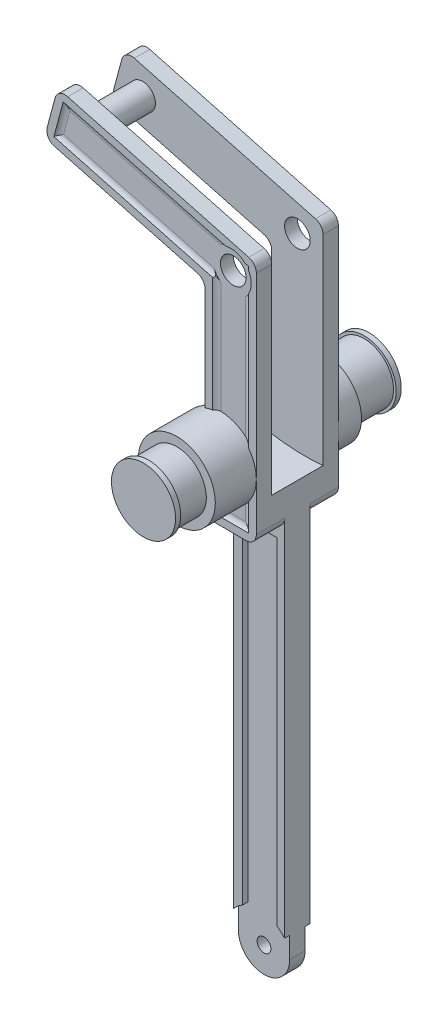
SolidWorks part; units mm, degrees
note: The reader was unsure of these and kept them because the rebuilt part matched: shared geometry of "Schizzo1<5>".
ref_plane "Piano frontale" through (0, 0, 0) normal (0, 0, 1) x (1, 0, 0)
ref_plane "Piano superiore" through (0, 0, 0) normal (0, 1, 0) x (1, 0, 0)
ref_plane "Piano destro" through (0, 0, 0) normal (1, 0, 0) x (0, 0, -1)
sketch "Schizzo1" plane through (0, 0, 0) normal (0, 0, 1) x (1, 0, 0)
  line L0 (0, -1.5347) -> (0, -38)
  line L9 (2, -40) -> (8, -40)
  line L10 (10, -38) -> (10, 6.1386)
  line L11 (8.5176, 8.0705) -> (-26.7741, 17.5268)
  line L12 (-29.2235, 16.1126) -> (-30.7765, 10.3171)
  line L13 (-29.3622, 7.8676) -> (-1.4824, 0.3972)
  line L14 (-19.0466, 15.4563) -> (-21.6348, 5.797) construction
  line L15 (-21.6348, 5.797) -> (-20.3407, 10.6267) construction
  line L16 (-20.3407, 10.6267) -> (-30, 13.2149) construction
  line L17 (-30, 13.2149) -> (-29.4183, 13.059) construction
  arc A0 (2, -40) -> (0, -38) centre (2, -38) cw
  arc A1 (8, -40) -> (10, -38) centre (8, -38) ccw
  arc A2 (0, -1.5347) -> (-1.4824, 0.3972) centre (-2, -1.5347) ccw
  arc A3 (10, 6.1386) -> (8.5176, 8.0705) centre (8, 6.1386) ccw
  arc A4 (-29.2235, 16.1126) -> (-26.7741, 17.5268) centre (-27.2917, 15.595) cw
  arc A5 (-29.3622, 7.8676) -> (-30.7765, 10.3171) centre (-28.8446, 9.7994) cw
  point P2 (-30, 13.2149)
  point P19 (0, 0)
  dimension "D6" = 2
  dimension "D1" = 40
  dimension "D2" = 40
  dimension "D3" = 10
  dimension "D4" = 10
  dimension "D5" = 10
  dimension "D7" = 105
extrude "Estrusione-Estrusione1" add sketch "Schizzo1" against normal blind 3 contours L11 A4 L12 A5 L13 A2 L0 A0 L9 A1 L10 A3
sketch "Schizzo4" plane through (0, 0, -3) normal (0, 0, -1) x (-1, 0, 0)
  line L0 (-8.5176, 8.0705) -> (26.7741, 17.5268) construction
  line L3 (29.2235, 16.1126) -> (30.7765, 10.3171) construction
  circle A0 centre (25.1704, 11.9208) radius 2.5
  dimension "D3" = 5
  dimension "D1" = 5
  dimension "D2" = 5
extrude "Estrusione-Estrusione4" add sketch "Schizzo4" along normal blind 5
sketch "Schizzo5" plane through (0, 0, -3) normal (0, 0, -1) x (-1, 0, 0)
  line L0 (-10, -32.8544) -> (-10, -38)
  line L1 (-10, -38) -> (-10, 6.1386) construction
  line L2 (0, -32.477) -> (0, -38)
  line L3 (0, -1.5347) -> (0, -38) construction
  line L4 (-2, -40) -> (-8, -40)
  arc A0 (-2, -40) -> (0, -38) centre (-2, -38) ccw
  arc A1 (-10, -32.8544) -> (0, -32.477) centre (-6.4967, 6.9919) ccw
  arc A2 (-8, -40) -> (-10, -38) centre (-8, -38) cw
  dimension "D1" = 40
extrude "Estrusione-Estrusione5" add sketch "Schizzo5" along normal blind 10
mirror "Specchia5" of "Estrusione-Estrusione4", "Estrusione-Estrusione5"
extrude "Estrusione-Estrusione6" add sketch "Schizzo1<5>" against normal blind 3 from surface at -13 starting at face at (-27.6704, 11.9208, -13)
sketch "Schizzo1<5>" plane through (0, 0, 0) normal (0, 0, 1) x (1, 0, 0) same geometry as "Schizzo1"
ref_plane "Piano2" through (0, 0, -8) normal (0, 0, -1) x (-1, 0, 0)
sketch "Schizzo8" plane through (0, 0, -8) normal (0, 0, -1) x (-1, 0, 0)
  line L0 (-8, -40) -> (-2, -40)
  line L5 (0, -38) -> (0, -108)
  line L6 (-10, -38) -> (-10, -108)
  line L7 (-10, -108) -> (0, -108)
  arc A0 (-2, -40) -> (0, -38) centre (-2, -38) ccw
  arc A1 (-10, -38) -> (-8, -40) centre (-8, -38) ccw
  dimension "D1" = 70
extrude "Estrusione-Estrusione7" add sketch "Schizzo8" along normal mid plane 5 contours L5 L7 L6 A1 L0 A0
sketch "Schizzo9" plane through (0, 0, -16) normal (0, 0, -1) x (-1, 0, 0)
  line L0 (-8.5, -38.5) -> (-8.5, 6.5223)
  line L1 (-8.5, 6.5223) -> (27.6452, 16.2074)
  line L2 (27.6452, 16.2074) -> (29.457, 9.4459)
  line L3 (29.457, 9.4459) -> (-1.5, 1.151)
  line L4 (-1.5, 1.151) -> (-1.5, -38.5)
  line L5 (-1.5, -38.5) -> (-8.5, -38.5)
  line L6 (-10, -38) -> (-10, 6.1386) construction
  line L7 (0, -1.5347) -> (0, -38) construction
  line L8 (-8.5176, 8.0705) -> (26.7741, 17.5268) construction
  line L10 (29.2235, 16.1126) -> (30.7765, 10.3171) construction
  line L11 (-8, -40) -> (-2, -40) construction
  line L12 (29.3622, 7.8676) -> (1.4824, 0.3972) construction
  dimension "D1" = 1.5
  dimension "D2" = 1.5
  dimension "D3" = 1.5
  dimension "D4" = 1.5
  dimension "D5" = 1.5
  dimension "D6" = 1.5
extrude "Taglio-Estrusione1" cut sketch "Schizzo9" against normal mid plane 1
sketch "Schizzo10" plane through (0, 0, 0) normal (0, 0, 1) x (1, 0, 0)
  line L1 (8.5, 6.5223) -> (-27.6452, 16.2074)
  line L2 (-27.6452, 16.2074) -> (-29.457, 9.4459)
  line L4 (8.5, -0.7247) -> (8.5, -38.5)
  line L5 (8.5, -38.5) -> (1.5, -38.5)
  line L6 (8.5, 6.5223) -> (8.5, -0.7247)
  line L7 (-29.457, 9.4459) -> (1.5, 1.151)
  line L8 (1.5, 1.151) -> (1.5, -38.5)
  line L9 (8.5176, 8.0705) -> (-26.7741, 17.5268) construction
  line L10 (-29.2235, 16.1126) -> (-30.7765, 10.3171) construction
  line L12 (0, -1.5347) -> (0, -38) construction
  line L13 (10, -38) -> (10, 6.1386) construction
  line L14 (2, -40) -> (8, -40) construction
  line L15 (-29.3622, 7.8676) -> (-1.4824, 0.3972) construction
  dimension "D1" = 1.5
  dimension "D2" = 1.5
  dimension "D3" = 1.5
  dimension "D4" = 1.5
  dimension "D5" = 1.5
  dimension "D6" = 1.5
extrude "Taglio-Estrusione2" cut sketch "Schizzo10" against normal mid plane 1
fillet "Raccordo1" radius 1.5 12 edges at (5, -38.5, -0.5) (8.5, -15.9889, -0.5) (1.5, -18.6745, -0.5) (-13.9785, 5.2984, -0.5) (-28.5511, 12.8266, -0.5) (-9.5726, 11.3648, -0.5) (1.5, -18.6745, -15.5) (5, -38.5, -15.5) (8.5, -15.9889, -15.5) (-9.5726, 11.3648, -15.5) (-28.5511, 12.8266, -15.5) (-13.9785, 5.2984, -15.5)
sketch "Schizzo13" plane through (0, 0, -0.5) normal (0, 0, 1) x (1, 0, 0)
  line L0 (0, -1.5347) -> (0, -38) construction
  line L1 (8.5176, 8.0705) -> (-26.7741, 17.5268) construction
  circle A0 centre (5, 3.8366) radius 2.5
  dimension "D3" = 5
  dimension "D1" = 5
  dimension "D2" = 5
extrude "Taglio-Estrusione5" cut sketch "Schizzo13" against normal mid plane 550
sketch "Schizzo14" plane through (0, -108, 0) normal (0, -1, 0) x (1, 0, 0)
  line L5 (0, -5.5) -> (10, -5.5)
  line L6 (0, -5.5) -> (0, -10.5)
  line L7 (0, -10.5) -> (10, -10.5)
  line L8 (10, -5.5) -> (10, -10.5)
extrude "Estrusione-Estrusione8" add sketch "Schizzo14" along normal blind 10
sketch "Schizzo16" plane through (0, 0, -5.5) normal (0, 0, 1) x (1, 0, 0)
  line L0 (10, -118) -> (0, -118) construction
  line L1 (10, -38) -> (10, -118) construction
  line L2 (0, -113) -> (-2.5239, -113)
  line L4 (-2.5239, -113) -> (-2.5239, -123.194)
  line L9 (-2.5239, -123.194) -> (14.5898, -123.194)
  line L10 (14.5898, -123.194) -> (14.5898, -113)
  line L11 (14.5898, -113) -> (10, -113)
  arc A1 (0, -113) -> (10, -113) centre (5, -113) ccw
  dimension "D3" = 10
  dimension "D1" = 5
  dimension "D2" = 5
extrude "Taglio-Estrusione6" cut sketch "Schizzo16" against normal blind 10
sketch "Schizzo17" plane through (0, 0, -5.5) normal (0, 0, 1) x (1, 0, 0)
  line L0 (0, -38) -> (0, -113) construction
  circle A0 centre (5, -113) radius 1.35
  arc A1 (0, -113) -> (10, -113) centre (5, -113) ccw construction
  point P7 (5, -118)
  dimension "D1" = 2.7
  dimension "D2" = 5
  dimension "D3" = 5
extrude "Taglio-Estrusione7" cut sketch "Schizzo17" against normal blind 10
sketch "Schizzo18" plane through (0, 0, -10.5) normal (0, 0, -1) x (-1, 0, 0)
  line L0 (-8.5, -42) -> (-1.5, -42)
  line L1 (-1.5, -42) -> (-1.5, -107.5543)
  line L2 (-8.5, -42) -> (-8.5, -107.5543)
  line L3 (-10, -38) -> (-10, -113) construction
  line L4 (0, -38) -> (0, -113) construction
  line L5 (-8, -40) -> (-2, -40) construction
  line L6 (-1.5, -107.5543) -> (-8.5, -107.5543) construction
  arc A1 (-8.5, -107.5543) -> (-1.5, -107.5543) centre (-5, -113) ccw
  dimension "D1" = 1.5
  dimension "D2" = 1.5
  dimension "D3" = 2
  dimension "D4" = 65.5543
extrude "Taglio-Estrusione8" cut sketch "Schizzo18" against normal blind 1
sketch "Schizzo19" plane through (0, 0, -5.5) normal (0, 0, 1) x (1, 0, 0)
  line L0 (1.829, -42) -> (1.829, -107.3523)
  line L1 (1.829, -42) -> (8.5, -42)
  line L2 (8.5, -42) -> (8.5, -107.55)
  line L3 (10, -38) -> (10, -113) construction
  line L4 (0, -38) -> (0, -113) construction
  line L6 (2, -40) -> (8, -40) construction
  arc A0 (1.829, -107.3523) -> (8.5, -107.55) centre (5, -113) ccw
  dimension "D1" = 1.5
  dimension "D2" = 1.829
  dimension "D3" = 2
  dimension "D5" = 65.55
extrude "Taglio-Estrusione9" cut sketch "Schizzo19" against normal blind 1 contours L0 A0 L2 L1
sketch "Schizzo20" plane through (0, 0, -0.5) normal (0, 0, 1) x (1, 0, 0)
  circle A0 centre (5, 3.8366) radius 4
  dimension "D1" = 8
extrude "Taglio-Estrusione10" cut sketch "Schizzo20" along normal blind 4
sketch "Schizzo21" plane through (0, 0, -0.5) normal (0, 0, 1) x (1, 0, 0)
  line L0 (5, 3.8366) -> (5, -28.6634) construction
  line L1 (7.5, 3.8366) -> (5, 3.8366) construction
  line L2 (5, -28.6634) -> (2.5, -28.6634) construction
  circle A0 centre (2.5, -28.6634) radius 7.5
  arc A2 (7.382, 3.0775) -> (7.382, 4.5957) centre (5, 3.8366) ccw construction
  dimension "D1" = 15
  dimension "D2" = 32.5
  dimension "D3" = 2.5
extrude "Estrusione-Estrusione9" add sketch "Schizzo21" along normal blind 8.5
fillet "Raccordo6" radius 2 1 edges at (0, -28.6634, -0.5)
sketch "Schizzo22" plane through (10, 0, 0) normal (1, 0, 0) x (0, 0, -1)
  line L1 (-8.5667, -12.2342) -> (24.6961, -12.2342)
  line L2 (-8.5667, -12.2342) -> (-8.5667, -42.9879)
  line L3 (-8.5667, -42.9879) -> (24.6961, -42.9879)
  line L4 (24.6961, -12.2342) -> (24.6961, -42.9879)
sketch "Schizzo23" plane through (0, 0, -15.5) normal (0, 0, -1) x (-1, 0, 0)
  line L0 (-7.5, 3.8366) -> (-5, 3.8366) construction
  line L1 (-5, 3.8366) -> (-5, -28.6634) construction
  line L2 (-5, -28.6634) -> (-2.5, -28.6634) construction
  arc A0 (-7.382, 4.5957) -> (-7.382, 3.0775) centre (-5, 3.8366) ccw construction
  circle A2 centre (-2.5, -28.6634) radius 7.5
  dimension "D2" = 2.5
  dimension "D3" = 15
  dimension "D1" = 32.5
extrude "Estrusione-Estrusione10" add sketch "Schizzo23" along normal blind 5 contours A2
fillet "Raccordo9" radius 2 1 edges at (0, -28.6634, -15.5)
sketch "Schizzo25" plane through (0, 0, 8) normal (0, 0, 1) x (1, 0, 0)
  line L0 (2.5, -21.1634) -> (2.5, -28.6634) construction
  circle A0 centre (2.5, -28.6634) radius 7.5 construction
  circle A1 centre (2.5, -28.6634) radius 5.75
  dimension "D1" = 11.5
extrude "Estrusione-Estrusione11" add sketch "Schizzo25" along normal blind 6.5
sketch "Schizzo26" plane through (0, 0, -20.5) normal (0, 0, -1) x (-1, 0, 0)
  line L0 (-2.5, -21.1634) -> (-2.5, -28.6634) construction
  circle A0 centre (-2.5, -28.6634) radius 7.5 construction
  arc A1 (-1.5, -21.2303) -> (-2.618, -21.1643) centre (-2.5, -28.6634) ccw construction
  circle A2 centre (-2.5, -28.6634) radius 5.75
  dimension "D1" = 11.5
extrude "Estrusione-Estrusione12" add sketch "Schizzo26" along normal blind 9
sketch "Schizzo28" plane through (0, 0, 14.5) normal (0, 0, 1) x (1, 0, 0)
  circle A0 centre (2.5, -28.6634) radius 6.25
  dimension "D1" = 12.5
extrude "Estrusione-Estrusione13" add sketch "Schizzo28" against normal blind 1
sketch "Schizzo29" plane through (0, 0, -29.5) normal (0, 0, -1) x (-1, 0, 0)
  circle A0 centre (-2.5, -28.6634) radius 6.25
  dimension "D1" = 12.5
extrude "Estrusione-Estrusione14" add sketch "Schizzo29" against normal blind 1
equation "\"alfa\"= 15gradi"
equation "\"D7@Schizzo1\"=90+\"alfa\""
